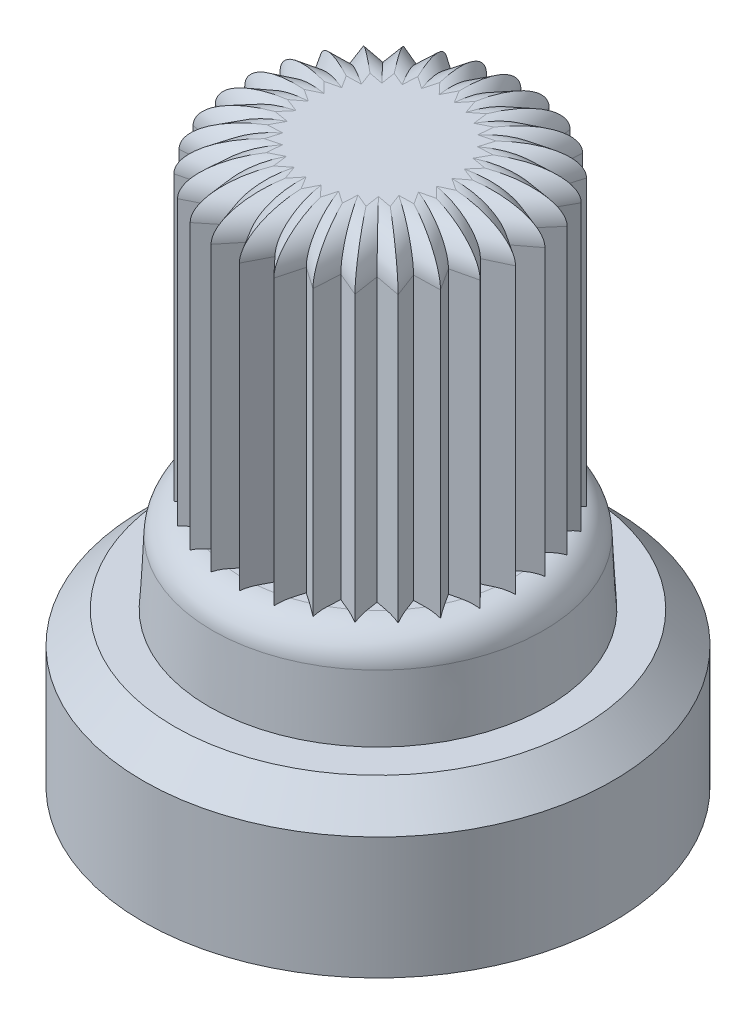
SolidWorks part; units mm, degrees
ref_plane "Спереди" through (0, 0, 0) normal (0, 0, 1) x (1, 0, 0)
ref_plane "Сверху" through (0, 0, 0) normal (0, 1, 0) x (1, 0, 0)
ref_plane "Справа" through (0, 0, 0) normal (1, 0, 0) x (0, 0, -1)
sketch "Sketch1" plane through (0, 0, 0) normal (0, 1, 0) x (1, 0, 0)
  circle A0 centre (0, 0) radius 7.5
  dimension "D1" = 15
extrude "Boss-Extrude1" add sketch "Sketch1" along normal blind 18
sketch "Sketch2" plane through (0, 0, 0) normal (0, -1, 0) x (1, 0, 0)
  circle A0 centre (0, 0) radius 6.5
  dimension "D1" = 13
extrude "Cut-Extrude1" cut sketch "Sketch2" against normal blind 0.1
sketch "Sketch3" plane through (0, 0.1, 0) normal (0, -1, 0) x (1, 0, 0)
  line L0 (-1.9498, -2.6624) -> (3.266, -0.4725)
  line L1 (0.6581, -1.5674) -> (-1.2775, 3.0427) construction
  circle A0 centre (0, 0) radius 3.3 construction
  arc A1 (-1.9498, -2.6624) -> (3.266, -0.4725) centre (0, 0) cw
  dimension "D1" = 6.6
  dimension "D2" = 5
extrude "Cut-Extrude2" cut sketch "Sketch3" against normal blind 14
chamfer "Chamfer1" distance 1 angle 30 1 edges at (0, 0, -6.5) first distance on face at (0, 0.1, -6.5)
sketch "Sketch4" plane through (0, 18, 0) normal (0, 1, 0) x (1, 0, 0)
  circle A0 centre (0, 0) radius 5.5
  dimension "D1" = 11
extrude "Cut-Extrude3" cut sketch "Sketch4" against normal blind 13 flip side to cut
chamfer "Chamfer2" distance 15 angle 3 1 edges at (0, 18, 5.5) first distance on face at (0, 5, 5.5)
chamfer "Chamfer3" distance 1 angle 45 1 edges at (0, 5, 7.5)
sketch "Sketch5" plane through (0, 18, 0) normal (0, 1, 0) x (1, 0, 0)
  line L0 (3.5975, 1.7486) -> (4.4295, 1.6124)
  line L1 (4.4295, 1.6124) -> (3.8798, 0.9732)
  line L2 (3.8798, 0.9732) -> (4.6653, 0.667)
  line L3 (4.6653, 0.667) -> (3.9947, 0.156)
  line L4 (3.9947, 0.156) -> (4.6993, -0.3068)
  line L5 (4.6993, -0.3068) -> (3.9371, -0.6672)
  line L6 (3.9371, -0.6672) -> (4.5302, -1.2664)
  line L7 (4.5302, -1.2664) -> (3.7097, -1.4604)
  line L8 (3.7097, -1.4604) -> (4.1652, -2.1699)
  line L9 (4.1652, -2.1699) -> (3.3223, -2.1891)
  line L10 (3.3223, -2.1891) -> (3.6203, -2.9777)
  line L11 (3.6203, -2.9777) -> (2.7919, -2.8212)
  line L12 (2.7919, -2.8212) -> (2.9195, -3.6546)
  line L13 (2.9195, -3.6546) -> (2.1417, -3.3293)
  line L14 (2.1417, -3.3293) -> (2.0931, -4.171)
  line L15 (2.0931, -4.171) -> (1.4, -3.6911)
  line L16 (1.4, -3.6911) -> (1.1775, -4.5043)
  line L17 (1.1775, -4.5043) -> (0.5993, -3.8908)
  line L18 (0.5993, -3.8908) -> (0.2126, -4.6399)
  line L19 (0.2126, -4.6399) -> (-0.2254, -3.9196)
  line L20 (-0.2254, -3.9196) -> (-0.7594, -4.572)
  line L21 (-0.7594, -4.572) -> (-1.0381, -3.7763)
  line L22 (-1.0381, -3.7763) -> (-1.6961, -4.3035)
  line L23 (-1.6961, -4.3035) -> (-1.8032, -3.4672)
  line L24 (-1.8032, -3.4672) -> (-2.5564, -3.846)
  line L25 (-2.5564, -3.846) -> (-2.4874, -3.0058)
  line L26 (-2.4874, -3.0058) -> (-3.3029, -3.2197)
  line L27 (-3.3029, -3.2197) -> (-3.0607, -2.4122)
  line L28 (-3.0607, -2.4122) -> (-3.9028, -2.4519)
  line L29 (-3.9028, -2.4519) -> (-3.498, -1.7124)
  line L30 (-3.498, -1.7124) -> (-4.33, -1.5762)
  line L31 (-4.33, -1.5762) -> (-3.7802, -0.937)
  line L32 (-3.7802, -0.937) -> (-4.5657, -0.6307)
  line L33 (-4.5657, -0.6307) -> (-3.8951, -0.1198)
  line L34 (-3.8951, -0.1198) -> (-4.5998, 0.3431)
  line L35 (-4.5998, 0.3431) -> (-3.8376, 0.7034)
  line L36 (-3.8376, 0.7034) -> (-4.4306, 1.3027)
  line L37 (-4.4306, 1.3027) -> (-3.6102, 1.4967)
  line L38 (-3.6102, 1.4967) -> (-4.0656, 2.2061)
  line L39 (-4.0656, 2.2061) -> (-3.2228, 2.2253)
  line L40 (-3.2228, 2.2253) -> (-3.5208, 3.014)
  line L41 (-3.5208, 3.014) -> (-2.6924, 2.8575)
  line L42 (-2.6924, 2.8575) -> (-2.8199, 3.6909)
  line L43 (-2.8199, 3.6909) -> (-2.0421, 3.3656)
  line L44 (-2.0421, 3.3656) -> (-1.9936, 4.2072)
  line L45 (-1.9936, 4.2072) -> (-1.3004, 3.7273)
  line L46 (-1.3004, 3.7273) -> (-1.078, 4.5405)
  line L47 (-1.078, 4.5405) -> (-0.4997, 3.927)
  line L48 (-0.4997, 3.927) -> (-0.113, 4.6762)
  line L49 (-0.113, 4.6762) -> (0.325, 3.9558)
  line L50 (0.325, 3.9558) -> (0.859, 4.6082)
  line L51 (0.859, 4.6082) -> (1.1377, 3.8126)
  line L52 (1.1377, 3.8126) -> (1.7956, 4.3397)
  line L53 (1.7956, 4.3397) -> (1.9028, 3.5035)
  line L54 (1.9028, 3.5035) -> (2.656, 3.8823)
  line L55 (2.656, 3.8823) -> (2.587, 3.042)
  line L56 (2.587, 3.042) -> (3.4024, 3.256)
  line L57 (3.4024, 3.256) -> (3.1602, 2.4484)
  line L58 (3.1602, 2.4484) -> (4.0024, 2.4882)
  line L59 (4.0024, 2.4882) -> (3.5975, 1.7486)
  circle A0 centre (0, 0) radius 4 construction
  circle A1 centre (0, 0) radius 4.7139 construction
  point P98 (0.0498, 0.0181)
  dimension "D1" = 8
  dimension "D2" = 30
extrude "Cut-Extrude4" cut sketch "Sketch5" against normal blind 10 flip side to cut
fillet "Fillet1" radius 1 1 edges at (0, 8, 5.238)
fillet "Fillet2" radius 1 60 edges at (4.1547, 18, -1.2928) (4.2726, 18, -0.8201) (4.33, 18, -0.4115) (4.347, 18, 0.0754) (4.3182, 18, 0.487) (4.2337, 18, 0.9668) (4.1199, 18, 1.3634) (3.9375, 18, 1.8152) (3.7438, 18, 2.1795) (3.4713, 18, 2.5834) (3.2061, 18, 2.8995) (2.8557, 18, 3.2379) (2.5306, 18, 3.492) (2.1174, 18, 3.7502) (1.7466, 18, 3.931) (1.2887, 18, 4.0977) (0.8884, 18, 4.1975) (0.4059, 18, 4.2653) (-0.0064, 18, 4.2798) (-0.4924, 18, 4.2458) (-0.8988, 18, 4.1742) (-1.3671, 18, 4.0399) (-1.7497, 18, 3.8853) (-2.1798, 18, 3.6566) (-2.5219, 18, 3.4259) (-2.8951, 18, 3.1128) (-3.1818, 18, 2.816) (-3.4817, 18, 2.4321) (-3.7004, 18, 2.0822) (-3.914, 18, 1.6443) (-4.0551, 18, 1.2566) (-4.173, 18, 0.7838) (-4.2304, 18, 0.3752) (-4.2475, 18, -0.1117) (-4.2187, 18, -0.5233) (-4.1341, 18, -1.0031) (-4.0204, 18, -1.3997) (-3.8379, 18, -1.8514) (-3.6442, 18, -2.2157) (-3.3718, 18, -2.6196) (-3.1066, 18, -2.9357) (-2.7561, 18, -3.2742) (-2.431, 18, -3.5282) (-2.0178, 18, -3.7864) (-1.647, 18, -3.9673) (-1.1892, 18, -4.1339) (-0.7888, 18, -4.2338) (-0.3064, 18, -4.3016) (0.106, 18, -4.316) (0.592, 18, -4.282) (0.9983, 18, -4.2104) (1.4667, 18, -4.0761) (1.8492, 18, -3.9216) (2.2794, 18, -3.6929) (2.6215, 18, -3.4622) (2.9947, 18, -3.149) (3.2813, 18, -2.8522) (3.5813, 18, -2.4683) (3.8, 18, -2.1184) (4.0135, 18, -1.6805)
sketch "Sketch7" plane through (0, 0.1, 0) normal (0, -1, 0) x (1, 0, 0)
  circle A0 centre (0, 0) radius 15.7261
extrude "Cut-Extrude6" cut sketch "Sketch7" along normal blind 10
chamfer "Chamfer4" distance 0.5 angle 60 2 edges at (0.6581, 0.1, -1.5674) (-1.2775, 0.1, 3.0427) first distance on face at (-0.3097, 0.1, 0.7376)
